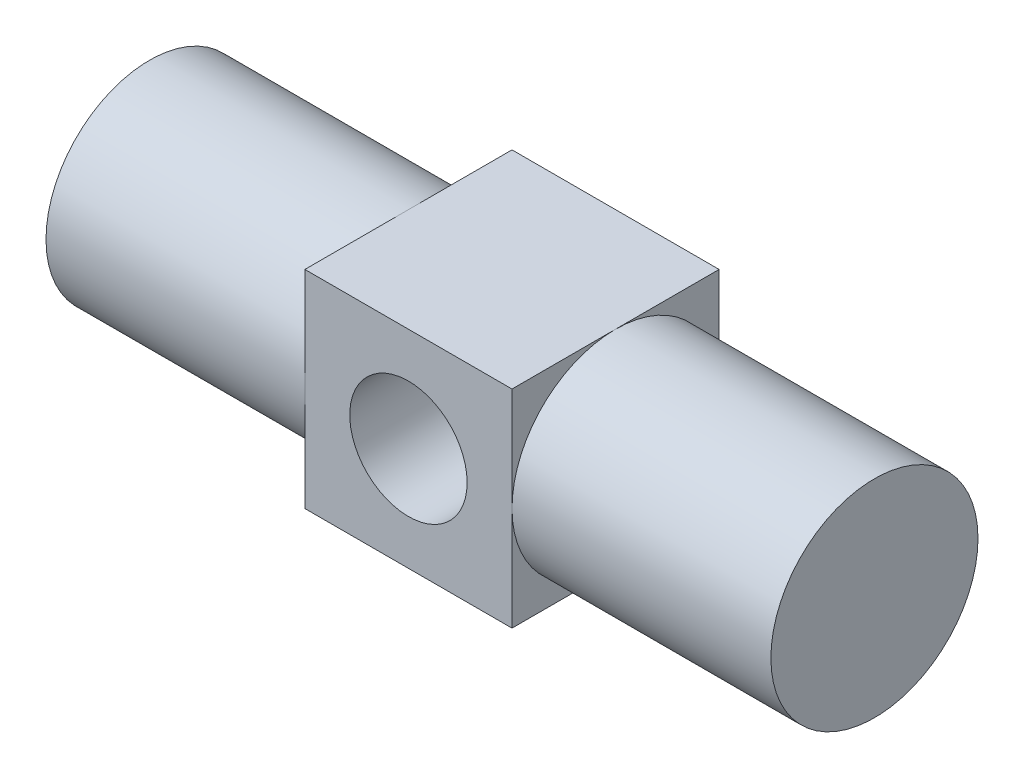
SolidWorks part; units mm, degrees
ref_plane "前视基准面" through (0, 0, 0) normal (0, 0, 1) x (1, 0, 0)
ref_plane "上视基准面" through (0, 0, 0) normal (0, 1, 0) x (1, 0, 0)
ref_plane "右视基准面" through (0, 0, 0) normal (1, 0, 0) x (0, 0, -1)
sketch "草图1" plane through (0, 0, 0) normal (0, 0, 1) x (1, 0, 0)
  line L1 (-6, -6) -> (6, -6)
  line L2 (-6, -6) -> (-6, 6)
  line L3 (-6, 6) -> (6, 6)
  line L4 (6, -6) -> (6, 6)
  line L5 (-6, -6) -> (6, 6) construction
  line L6 (-6, 6) -> (6, -6) construction
  point P0 (0, 0)
  dimension "D1" = 12
  dimension "D2" = 12
extrude "凸台-拉伸1" add sketch "草图1" along normal mid plane 12
sketch "草图2" plane through (6, 0, 0) normal (1, 0, 0) x (0, 0, -1)
  circle A0 centre (0, 0) radius 6
  point P3 (0, 0)
  point P7 (0, 6)
  point P8 (5.79, -1.5734)
  point P9 (0, 0)
  dimension "D1" = 12
extrude "凸台-拉伸2" add sketch "草图2" along normal blind 15
mirror "镜向1" about plane through (0, 0, 0) normal (1, 0, 0) of "凸台-拉伸2"
sketch "草图3" plane through (0, 0, 6) normal (0, 0, 1) x (1, 0, 0)
  point P0 (0, 0)
hole_wizard "M8 螺纹孔1" positions "3D草图1" profile "草图4" tap size "M8" standard "GB" end condition through all
sketch3d "3D草图1"
  point P0 (0, 0, 6)
sketch "草图4" plane through (0, 0, 6) normal (1, 0, 0) x (0, -1, 0)
  line L0 (0, 0) -> (0, 12)
  line L1 (0, 12) -> (3.4, 12)
  line L2 (3.4, 12) -> (3.4, 0)
  line L5 (3.4, 0) -> (0, 0)
  line L11 (0, -6.35) -> (0, 107.95) construction
  dimension "通孔螺纹孔钻头直径" = 6.8
  dimension "通孔螺纹孔钻头深度" = 12
cosmetic thread "孔螺蚊线1" parameters "D2"=8
